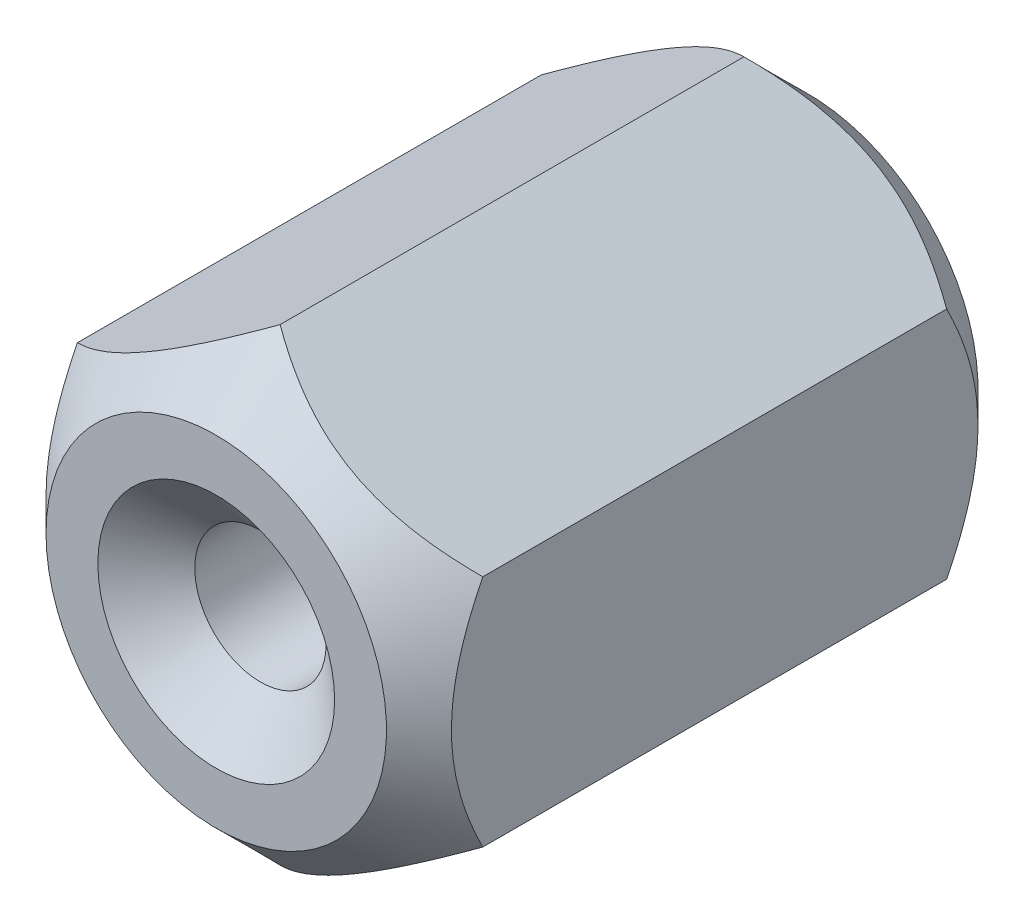
SolidWorks part; units mm, degrees
ref_plane "Front Plane" through (0, 0, 0) normal (0, 0, 1) x (1, 0, 0)
ref_plane "Top Plane" through (0, 0, 0) normal (0, 1, 0) x (1, 0, 0)
ref_plane "Right Plane" through (0, 0, 0) normal (1, 0, 0) x (0, 0, -1)
sketch "Sketch1" plane through (0, 0, 0) normal (0, 0, 1) x (1, 0, 0)
  line L1 (3.175, -1.8331) -> (3.175, 1.8331)
  line L2 (3.175, 1.8331) -> (0, 3.6662)
  line L3 (0, 3.6662) -> (-3.175, 1.8331)
  line L4 (-3.175, 1.8331) -> (-3.175, -1.8331)
  line L5 (-3.175, -1.8331) -> (0, -3.6662)
  line L6 (0, -3.6662) -> (3.175, -1.8331)
  circle A0 centre (0, 0) radius 3.175 construction
  dimension "D1" = 6.35
extrude "Boss-Extrude1" add sketch "Sketch1" along normal blind 4.6325 and the other way blind 4.6325
ref_axis "Axis1" through (0, 0, -0.635) along (0, 0, 1)
sketch "Sketch3" plane through (0, 0, 0) normal (1, 0, 0) x (0, 0, -1)
  line L0 (-4.6325, 3.6662) -> (4.6325, 3.6662) construction
  line L1 (-3.6325, 3.6662) -> (-4.6325, 2.6662)
  line L2 (-4.6325, 1.8331) -> (-4.6325, 3.6662) construction
  line L3 (-4.6325, 2.6662) -> (-4.6325, 3.6662)
  line L4 (-4.6325, 3.6662) -> (-3.6325, 3.6662)
  dimension "D1" = 1
  dimension "D2" = 45
revolve "Cut-Revolve2" cut sketch "Sketch3" angle 360 about axis through (0, 0, -0.635) along (0, 0, 1)
mirror "Mirror1" about plane through (0, 0, 0) normal (0, 0, 1) of "Cut-Revolve2"
hole_wizard "CSK for #1 Flat Head Machine Screw (100)1" positions "Sketch5" profile "Sketch4" countersink size "#1" standard "ANSI Inch" end condition through all
sketch "Sketch5" plane through (0, 0, 4.6325) normal (0, 0, 1) x (1, 0, 0)
  point P0 (0, 0)
sketch "Sketch4" plane through (0, 0, 4.6325) normal (1, 0, 0) x (0, -1, 0)
  line L0 (0, 0) -> (0, 9.265)
  line L1 (0, 9.265) -> (1.6637, 9.265)
  line L2 (1.0287, 8.63) -> (1.0287, 0.6927)
  line L3 (1.0287, 0.6927) -> (1.8542, 0)
  line L5 (1.8542, 0) -> (0, 0)
  line L6 (-1.0287, 0.6927) -> (-1.8542, 0) construction
  line L7 (1.6637, 9.265) -> (1.0287, 8.63)
  line L8 (-1.6637, 9.265) -> (-1.0287, 8.63) construction
  line L11 (0, -6.35) -> (0, 107.95) construction
  dimension "Thru Hole Dia." = 2.0574
  dimension "Thru Hole Depth" = 9.265
  dimension "Near C'Sink Dia." = 3.7084
  dimension "Near C'Sink Angle" = 100
  dimension "Far C'Sink Dia." = 3.3274
  dimension "Far C'Sink Angle" = 90
